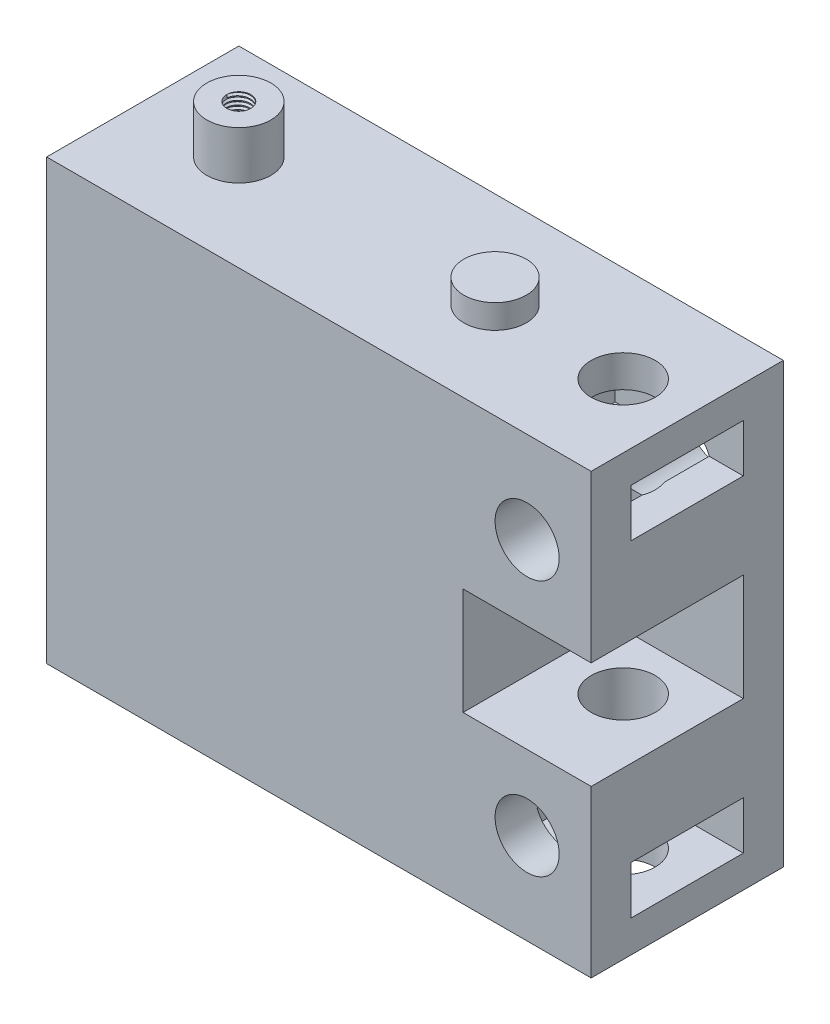
SolidWorks part; units mm, degrees
ref_plane "前视基准面" through (0, 0, 0) normal (0, 0, 1) x (1, 0, 0)
ref_plane "上视基准面" through (0, 0, 0) normal (0, 1, 0) x (1, 0, 0)
ref_plane "右视基准面" through (0, 0, 0) normal (1, 0, 0) x (0, 0, -1)
other "Configuration Table"
sketch "草图1" plane through (0, 0, 0) normal (0, 0, 1) x (1, 0, 0)
  line L1 (0, 0) -> (34, 0)
  line L2 (0, 0) -> (0, 27.4)
  line L3 (0, 27.4) -> (34, 27.4)
  line L4 (34, 0) -> (34, 27.4)
  dimension "D1" = 34
  dimension "D2" = 27.4
extrude "凸台-拉伸1" add sketch "草图1" along normal blind 12
sketch "草图2" plane through (0, 27.4, 0) normal (0, 1, 0) x (1, 0, 0)
  line L0 (0, -12) -> (0, 0) construction
  circle A0 centre (6, -6) radius 2
  point P4 (0, -6)
  dimension "D1" = 4
  dimension "D2" = 6
extrude "凸台-拉伸2" add sketch "草图2" along normal blind 3
sketch "草图3" plane through (0, 0, 0) normal (0, -1, 0) x (1, 0, 0)
  circle A0 centre (6, 6) radius 1.95
  circle A1 centre (22, 6) radius 1.95
  dimension "D2" = 3.9
  dimension "D3" = 3.9
  dimension "D1" = 16
extrude "凸台-拉伸3" add sketch "草图3" along normal blind 1.5
sketch "草图4" plane through (0, 27.4, 0) normal (0, 1, 0) x (1, 0, 0)
  circle A0 centre (22, -6) radius 1.95
  circle A1 centre (22, -6) radius 1.95 construction
extrude "凸台-拉伸4" add sketch "草图4" along normal blind 1.5
sketch "草图5" plane through (0, 30.4, 0) normal (0, 1, 0) x (1, 0, 0)
  circle A0 centre (6, -6) radius 0.75
  dimension "D1" = 1.5
extrude "切除-拉伸2" cut sketch "草图5" against normal blind 3
thread "螺纹线1" pitch 0.25 method cut profile "螺纹线轮廓1" start angle 0, offset 0, length 2, pitch 0.25, diameter 1.5
ref_plane "基准面1" through (5.25, 30.4, 6) normal (0, 0, 1) x (-1, 0, 0)
sketch "螺纹线轮廓1" plane through (5.25, 30.4, 6) normal (0, 0, 1) x (-1, 0, 0)
  line L0 (0, 0) -> (0, 0.25) construction
  line L1 (0, 0) -> (0.1353, 0.0781)
  line L2 (0.1353, 0.0781) -> (0.1353, 0.1094)
  line L3 (0.1353, 0.1094) -> (0, 0.1875)
  line L4 (0.1353, 0.0937) -> (0, 0.0937) construction
  line L11 (0, 0) -> (0, 0.1875)
  point P2 (0, 0)
  dimension "Pitch" = 0.25
  dimension "Profile_Angle" = 60
  dimension "Profile_Land" = 0.0312
  dimension "Profile_Height" = 0.1353
sketch "草图8" plane through (0, 27.4, 0) normal (0, 1, 0) x (1, 0, 0)
  line L0 (34, -12) -> (34, 0) construction
  circle A0 centre (30, -6) radius 2
  point P4 (34, -6)
  dimension "D1" = 4
  dimension "D2" = 4
extrude "切除-拉伸3" cut sketch "草图8" against normal through all
sketch "草图9" plane through (34, 0, 0) normal (1, 0, 0) x (0, 0, -1)
  line L0 (-12, 0) -> (-12, 27.4) construction
  line L1 (-9.5, 25.4) -> (-2.5, 25.4)
  line L2 (-9.5, 25.4) -> (-9.5, 22.4)
  line L3 (-9.5, 22.4) -> (-2.5, 22.4)
  line L4 (-2.5, 25.4) -> (-2.5, 22.4)
  line L5 (-9.5, 5) -> (-2.5, 5)
  line L6 (-9.5, 5) -> (-9.5, 2)
  line L7 (-9.5, 2) -> (-2.5, 2)
  line L8 (-2.5, 5) -> (-2.5, 2)
  line L9 (-12, 17.04) -> (-2.5, 17.04)
  line L10 (-12, 17.04) -> (-12, 10.36)
  line L11 (-12, 10.36) -> (-2.5, 10.36)
  line L12 (-2.5, 17.04) -> (-2.5, 10.36)
  line L13 (-6, 27.4) -> (-6, 0) construction
  line L14 (-5.25, 27.4) -> (-6.75, 27.4) construction
  line L15 (-12, 0) -> (0, 0) construction
  line L16 (0, 0) -> (0, 27.4) construction
  line L17 (-12, 27.4) -> (0, 27.4) construction
  point P24 (-12, 13.7)
  dimension "D1" = 7
  dimension "D2" = 3
  dimension "D3" = 7
  dimension "D4" = 3
  dimension "D5" = 6.68
  dimension "D6" = 2.5
  dimension "D7" = 2
  dimension "D8" = 2
extrude "切除-拉伸4" cut sketch "草图9" against normal blind 8
sketch "草图10" plane through (0, 0, 12) normal (0, 0, 1) x (1, 0, 0)
  line L0 (34, 17.04) -> (34, 27.4) construction
  line L1 (34, 13.7) -> (26, 13.7) construction
  line L2 (34, 10.36) -> (34, 17.04) construction
  line L3 (26, 17.04) -> (26, 10.36) construction
  circle A0 centre (30, 21.7) radius 2
  circle A1 centre (30, 5.7) radius 2
  dimension "D2" = 4
  dimension "D3" = 4
  dimension "D4" = 16
extrude "切除-拉伸5" cut sketch "草图10" against normal through all
equation "\"D3@草图3\"=\"D2@草图3\""
